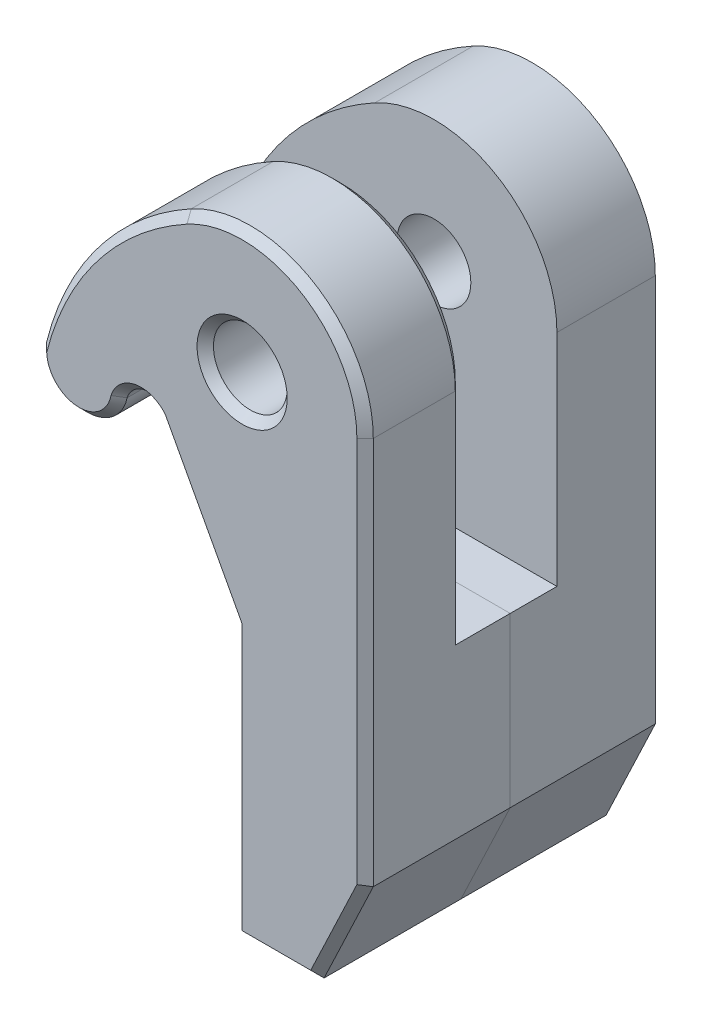
SolidWorks part; units mm, degrees
ref_plane "Front Plane" through (0, 0, 0) normal (0, 0, 1) x (1, 0, 0)
ref_plane "Top Plane" through (0, 0, 0) normal (0, 1, 0) x (1, 0, 0)
ref_plane "Right Plane" through (0, 0, 0) normal (1, 0, 0) x (0, 0, -1)
sketch "Sketch1" plane through (0, 0, 0) normal (0, 0, 1) x (1, 0, 0)
  line L0 (7.5, 0) -> (7.5, -23.6787)
  line L1 (7.5, -23.6787) -> (4.5, -30)
  line L2 (4.5, -30) -> (-0.5, -30)
  line L3 (-0.5, -30) -> (-0.5, -13.4164)
  line L4 (-0.5, -13.4164) -> (-5.105, -4.8541)
  arc A0 (7.5, 0) -> (-3.604, 6.5773) centre (0, 0) ccw
  circle A1 centre (0, 0) radius 2.25
  arc A2 (-3.604, 6.5773) -> (-12.4198, -4.8541) centre (5.0456, -9.2082) ccw
  arc A4 (-12.4198, -4.8541) -> (-7.5132, -5.3593) centre (-9.9405, -4.8541) ccw
  arc A5 (-7.5132, -5.3593) -> (-5.105, -4.8541) centre (-6.165, -5.794) cw
  dimension "D1" = 15
  dimension "D2" = 4.5
  dimension "D3" = 8
  dimension "D7" = 36
  dimension "D4" = 5
  dimension "D6" = 6.9971
extrude "Boss-Extrude1" add sketch "Sketch1" along normal blind 6
ref_plane "Plane1" through (0, 0, -2.85) normal (0, 0, -1) x (-1, 0, 0)
sketch "Sketch2" plane through (0, 0, 0) normal (0, 0, -1) x (-1, 0, 0)
  line L1 (0.5, -13.4164) -> (-7.5, -13.4164)
  line L6 (-7.5, 0) -> (-7.5, -23.6787)
  line L7 (-7.5, -23.6787) -> (-4.5, -30)
  line L8 (-4.5, -30) -> (0.5, -30)
  line L9 (0.5, -30) -> (0.5, -13.4164)
  line L10 (0.5, -13.4164) -> (5.105, -4.8541)
  line L12 (-7.5, -13.4164) -> (-7.5, -23.6787)
  line L13 (-7.5, -23.6787) -> (-4.5, -30)
  line L14 (-4.5, -30) -> (0.5, -30)
  line L15 (0.5, -30) -> (0.5, -13.4164)
  arc A4 (7.5132, -5.3593) -> (5.105, -4.8541) centre (6.165, -5.794) ccw
  arc A5 (7.5132, -5.3593) -> (5.105, -4.8541) centre (6.165, -5.794) ccw
  arc A6 (7.5132, -5.3593) -> (12.4198, -4.8541) centre (9.9405, -4.8541) ccw
  arc A7 (3.604, 6.5773) -> (-7.5, 0) centre (0, 0) ccw
  arc A8 (7.5132, -5.3593) -> (12.4198, -4.8541) centre (9.9405, -4.8541) ccw
  arc A13 (12.4198, -4.8541) -> (3.604, 6.5773) centre (-5.0456, -9.2082) ccw
  dimension "D1" = 0
extrude "Boss-Extrude2" add sketch "Sketch2" along direction (0, 0, -1) on the side of the normal up to surface (2.85 mm away) up to plane "Plane1"
ref_plane "Plane2" through (8.5, 0, 0) normal (1, 0, 0) x (0, 0, -1)
mirror "Mirror2" about plane through (0, 0, -2.85) normal (0, 0, -1) of bodies 103 101
mirror "Mirror4" [suppressed] about plane through (8.5, 0, 0) normal (1, 0, 0)
chamfer "Chamfer1" distance 0.5 angle 45 10 edges at (2.25, 0, 6) (7.5, -11.8394, 6) (6, -26.8394, 6) (2, -30, 6) (-0.5, -21.7082, 6) (-2.8025, -9.1353, 6) (-6.4558, -4.4076, 6) (-10.1945, -7.3204, 6) (-9.2081, 1.7841, 6) (3.8223, 6.4529, 6)
chamfer "Chamfer2" [suppressed] distance 0.5 angle 45
chamfer "Chamfer3" [suppressed] distance 0.5 angle 45
chamfer "Chamfer4" distance 0.5 angle 45 7 edges at (2.25, 0, 0) (3.8223, 6.4529, 0) (-9.2081, 1.7841, 0) (-10.1945, -7.3204, 0) (-6.4558, -4.4076, 0) (-2.8025, -9.1353, 0)
